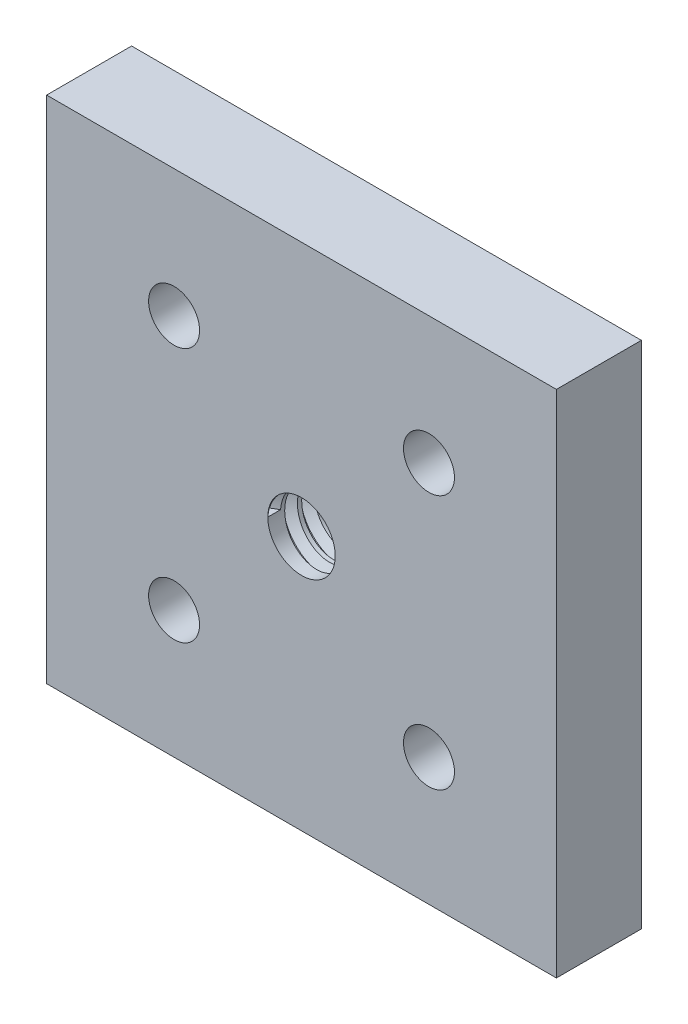
SolidWorks part; units mm, degrees
ref_plane "Front Plane" through (0, 0, 0) normal (0, 0, 1) x (1, 0, 0)
ref_plane "Top Plane" through (0, 0, 0) normal (0, 1, 0) x (1, 0, 0)
ref_plane "Right Plane" through (0, 0, 0) normal (1, 0, 0) x (0, 0, -1)
sketch "Sketch1" plane through (0, 0, 0) normal (0, 0, 1) x (1, 0, 0)
  line L1 (-30, -30) -> (30, -30)
  line L2 (-30, -30) -> (-30, 30)
  line L3 (-30, 30) -> (30, 30)
  line L4 (30, -30) -> (30, 30)
  line L5 (-30, -30) -> (30, 30) construction
  line L6 (-30, 30) -> (30, -30) construction
  point P0 (0, 0)
  point P19 (0, 0)
  dimension "D1" = 60
  dimension "D2" = 60
extrude "Boss-Extrude1" add sketch "Sketch1" along normal blind 10
sketch "Sketch2" plane through (0, 0, 10) normal (0, 0, 1) x (1, 0, 0)
  circle A0 centre (0, 0) radius 3.9688
extrude "Cut-Extrude1" cut sketch "Sketch2" against normal through all
thread "Thread1" pitch 2 method cut profile "Thread Profile1" start angle 0, offset 0, length 10, pitch 2, diameter 7.9375
ref_plane "Plane1" through (-3.9688, 0, 10) normal (0, -1, 0) x (-1, 0, 0)
sketch "Thread Profile1" plane through (-3.9688, 0, 10) normal (0, -1, 0) x (-1, 0, 0)
  line L0 (0, 0) -> (0, 2) construction
  line L1 (0, 0) -> (1.0825, 0.625)
  line L2 (1.0825, 0.625) -> (1.0825, 0.875)
  line L3 (1.0825, 0.875) -> (0, 1.5)
  line L4 (1.0825, 0.75) -> (0, 0.75) construction
  line L11 (0, 0) -> (0, 1.5)
  point P2 (0, 0)
  dimension "Pitch" = 2
  dimension "Profile_Angle" = 60
  dimension "Profile_Land" = 0.25
  dimension "Profile_Height" = 1.0825
sketch "Sketch3" plane through (0, 0, 10) normal (0, 0, 1) x (1, 0, 0)
  circle A8 centre (15, 15) radius 3
  circle A9 centre (-15, 15) radius 3
  circle A10 centre (-15, -15) radius 3
  circle A11 centre (15, -15) radius 3
  point P0 (0, 0)
  dimension "D1" = 30
  dimension "D2" = 30
extrude "Cut-Extrude2" cut sketch "Sketch3" against normal blind 10
